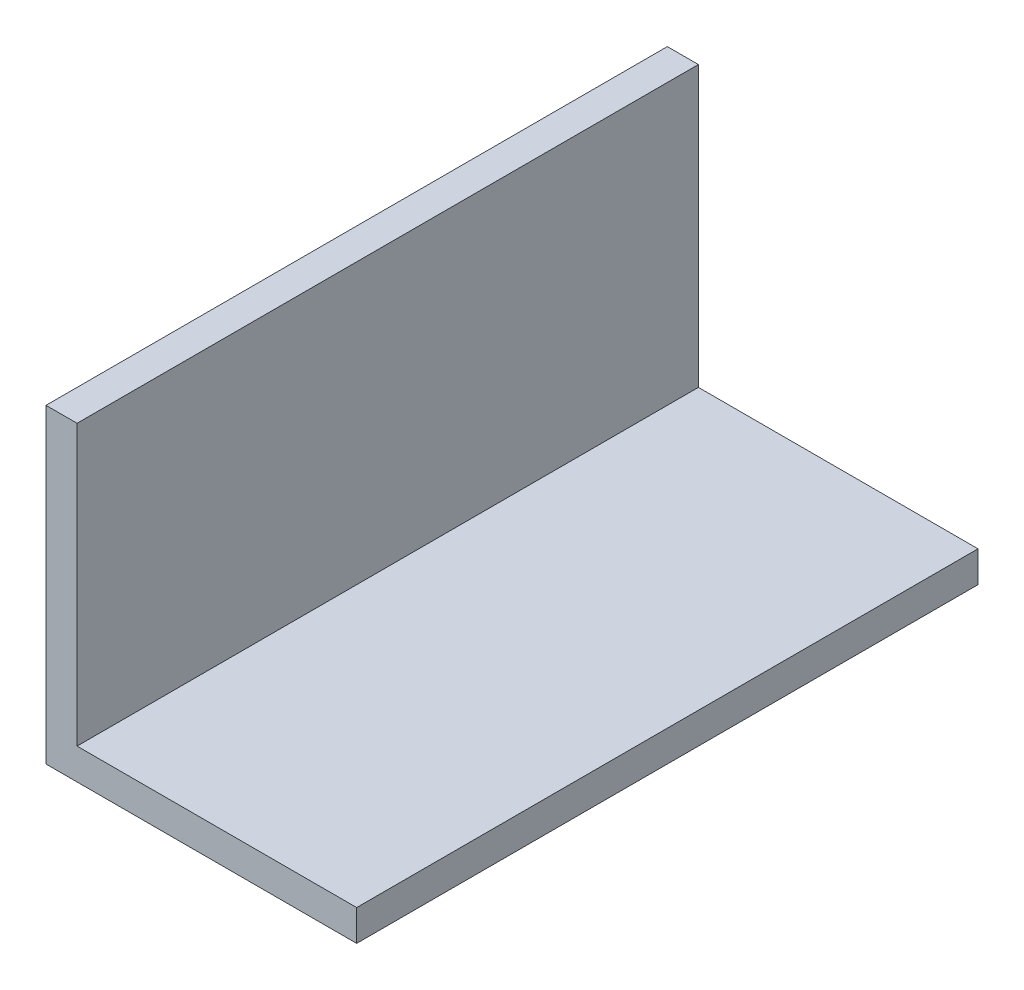
SolidWorks part; units mm, degrees
ref_plane "Спереди" through (0, 0, 0) normal (0, 0, 1) x (1, 0, 0)
ref_plane "Сверху" through (0, 0, 0) normal (0, 1, 0) x (1, 0, 0)
ref_plane "Справа" through (0, 0, 0) normal (1, 0, 0) x (0, 0, -1)
sketch "Эскиз1" plane through (0, 0, 0) normal (0, 0, 1) x (1, 0, 0)
  line L0 (0, 30) -> (0, 0)
  line L1 (0, 0) -> (30, 0)
  line L2 (0, 30) -> (3, 30)
  line L3 (3, 30) -> (3, 3)
  line L4 (3, 3) -> (30, 3)
  line L5 (30, 3) -> (30, 0)
extrude "Бобышка-Вытянуть1" add sketch "Эскиз1" along normal blind 60
